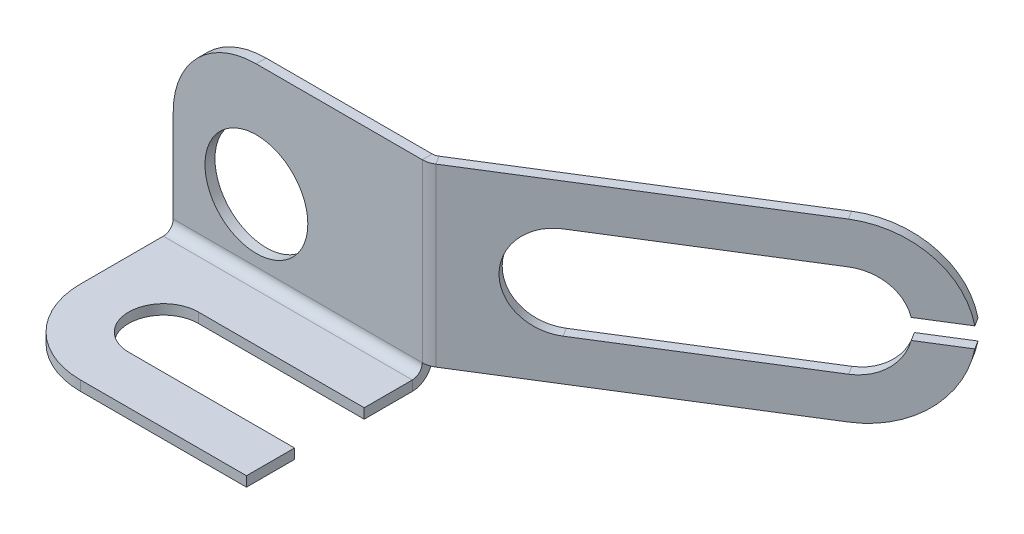
SolidWorks part; units mm, degrees
note: The reader was unsure of these and kept them because the rebuilt part matched: flange length of "Edge-Flange1", "Edge-Flange2".
ref_plane "Front Plane" through (0, 0, 0) normal (0, 0, 1) x (1, 0, 0)
ref_plane "Top Plane" through (0, 0, 0) normal (0, 1, 0) x (1, 0, 0)
ref_plane "Right Plane" through (0, 0, 0) normal (1, 0, 0) x (0, 0, -1)
sketch "Sketch1" plane through (0, 0, 0) normal (0, 1, 0) x (1, 0, 0)
  line L0 (-12.2638, 0) -> (10.2953, 0) construction
  line L1 (-8.4742, 5) -> (6.5404, 5)
  line L2 (-8.4742, 5) -> (-8.4742, 0)
  line L3 (-3.4742, -5) -> (6.5404, -5)
  line L5 (0, 0) -> (7.6969, 0) construction
  line L12 (6.5404, 5) -> (6.5404, -5)
  arc A0 (-8.4742, 0) -> (-3.4742, -5) centre (-3.4742, 0) ccw
  point P0 (0, 0)
  point P12 (3.8484, 0)
  dimension "D3" = 5
  dimension "D2" = 5
base flange "Base-Flange1" sketch "Sketch1" thickness 0.6 reverse thickness direction no parameters "D1"=0.7366
sketch "Sketch6" plane through (0, 0, 0) normal (0, 1, 0) x (1, 0, 0)
  line L0 (-8.4742, 0) -> (10.7229, 0) construction
  line L1 (6.5404, -2.1) -> (-3.4596, -2.1)
  line L2 (6.5404, -5) -> (6.5404, 5) construction
  line L3 (6.5404, 2.1) -> (-3.4596, 2.1)
  line L4 (6.5404, 2.1) -> (6.5404, -2.1)
  arc A0 (-3.4596, 2.1) -> (-3.4596, -2.1) centre (-3.4596, 0) ccw
  point P11 (0, 0)
  dimension "D2" = 2.1
  dimension "D1" = 10
extrude "Cut-Extrude1" cut sketch "Sketch6" against normal blind 10
edge flange "Edge-Flange1" sketch "Sketch9" flange angle 90 flange length 11.8 flange position bend outside bend radius 0.6 thickness 0.6 parameters "D6"=10
sketch "Sketch9" plane through (0, 0, -5) normal (0, 0, 1) x (1, 0, 0)
  line L2 (-8.4742, 0) -> (-8.4742, 11.2)
  line L3 (-8.4742, 11.2) -> (6.5404, 11.2)
  line L4 (6.5404, 11.2) -> (6.5404, 0)
  line L5 (6.5404, 0) -> (-8.4742, 0) construction
  line L6 (6.5404, 0) -> (-8.4742, 0)
bend "EdgeBend1" bend radius 0.6 bend angle 90 parameters "D5"=1
sketch "Sketch10" plane through (0, 0, -5.6) normal (0, 0, 1) x (1, 0, 0)
  line L0 (-8.4742, 11.2) -> (-8.4742, 0.6) construction
  line L1 (6.5404, 11.2) -> (-8.4742, 11.2) construction
  line L2 (-8.4742, 6.2) -> (-8.4742, 11.2)
  line L3 (-8.4742, 11.2) -> (-3.4742, 11.2)
  arc A0 (-8.4742, 6.2) -> (-3.4742, 11.2) centre (-3.4742, 6.2) cw
  dimension "D1" = 5
extrude "Cut-Extrude2" cut sketch "Sketch10" against normal blind 10
sketch "Sketch11" plane through (0, 0, -5.6) normal (0, 0, 1) x (1, 0, 0)
  line L0 (6.5404, -0.6) -> (-3.4596, -0.6) construction
  line L1 (6.5404, 0.6) -> (6.5404, 11.2) construction
  circle A0 centre (-3.4596, 4.4) radius 3.1
  point P4 (-3.1567, 4.4)
  point P5 (-3.7952, 4.4)
  dimension "D3" = 6.2
  dimension "D1" = 5
  dimension "D2" = 10
extrude "Cut-Extrude3" cut sketch "Sketch11" against normal blind 10
edge flange "Edge-Flange2" sketch "Sketch16" flange angle 148 flange length 24 flange position bend outside bend radius 0.6 thickness 0.6 parameters "D6"=10
sketch "Sketch16" plane through (6.5404, 0, -6.2) normal (-0.5299, 0, -0.848) x (0, 1, 0)
  line L2 (0.6, 0) -> (0.6, 23.828)
  line L3 (0.6, 23.828) -> (11.2, 23.828)
  line L4 (11.2, 23.828) -> (11.2, 0)
  line L5 (11.2, 0) -> (0.6, 0) construction
  line L6 (11.2, 0) -> (0.6, 0)
bend "EdgeBend2" bend radius 0.6 bend angle 32 parameters "D5"=2
sketch "Sketch17" plane through (-0.5834, 0, -0.9336) normal (0.5299, 0, 0.848) x (0.848, 0, -0.5299)
  line L0 (14.7141, 5.9) -> (27.2141, 5.9) construction
  line L1 (14.7141, 8.7) -> (27.2141, 8.7)
  line L2 (14.7141, 3.1) -> (27.2141, 3.1)
  line L3 (8.5141, 0.6) -> (8.5141, 11.2) construction
  line L4 (9.15, 11.2) -> (32.8059, 11.2) construction
  line L5 (32.8059, 11.2) -> (32.8059, 0.6) construction
  line L6 (32.8059, 0.6) -> (9.15, 0.6) construction
  line L7 (32.8059, 11.2) -> (32.8059, 0.6) construction
  line L8 (32.8059, 11.2) -> (32.8059, 0.6)
  line L9 (27.2059, 11.2) -> (32.8059, 11.2)
  line L10 (32.8059, 0.6) -> (27.2059, 0.6)
  arc A0 (14.7141, 8.7) -> (14.7141, 3.1) centre (14.7141, 5.9) ccw
  arc A1 (27.2141, 3.1) -> (27.2141, 8.7) centre (27.2141, 5.9) ccw
  arc A2 (27.2059, 11.2) -> (32.7979, 5.9) centre (27.2059, 5.6) cw
  arc A3 (27.2059, 0.6) -> (32.7979, 5.9) centre (27.2059, 6.2) ccw
  point P2 (20.9641, 5.9)
  dimension "D3" = 2.8
  dimension "D4" = 5.6
  dimension "D5" = 5.6
  dimension "D1" = 12.5
  dimension "D2" = 6.2
extrude "Cut-Extrude4" cut sketch "Sketch17" against normal blind 10
sketch "Sketch19" plane through (-0.5834, 0, -0.9336) normal (0.5299, 0, 0.848) x (0.848, 0, -0.5299)
  line L0 (32.7979, 5.9) -> (30.0141, 5.9) construction
  line L1 (32.7332, 5.3) -> (29.9491, 5.3)
  line L2 (32.7332, 6.5) -> (29.9491, 6.5)
  arc A0 (27.2141, 3.1) -> (27.2141, 8.7) centre (27.2141, 5.9) ccw construction
  arc A1 (27.2059, 0.6) -> (32.7979, 5.9) centre (27.2059, 6.2) ccw construction
  arc A2 (29.9491, 6.5) -> (29.9491, 5.3) centre (27.2141, 5.9) cw
  arc A3 (32.7332, 6.5) -> (32.7332, 5.3) centre (30.4025, 5.9) cw
  dimension "D1" = 0.6
extrude "Cut-Extrude5" cut sketch "Sketch19" against normal blind 10
sketch "Bend-Lines1" [suppressed] plane through (0, 0, 0) normal (0, 1, 0) x (1, 0, 0)
sketch "Bounding-Box1" [suppressed] plane through (0, 0, 0) normal (0, 1, 0) x (1, 0, 0)
sheet metal parameters "Sheet-Metal1" thickness 0.6 parameters "D1"=0.7366
flat pattern "Flat-Pattern1" [suppressed]
sketch "Bend-Lines2" plane through (0, 0, 0) normal (0, 1, 0) x (1, 0, 0)
sketch3d "Bounding-Box2" [suppressed]
  line L0 (5, -5, 0) -> (-10.0146, -5, 0) construction
  line L1 (5, 5, 0) -> (-10.0146, 5, 0) construction
  line L2 (5, -5, 0) -> (5, 5, 0) construction
  line L3 (-10.0146, -5, 0) -> (-10.0146, 5, 0) construction
sheet metal parameters "Sheet-Metal2" thickness 0.6 parameters "D1"=0.7366
flat pattern "Flat-Pattern1"
sketch "Bend-Lines2" plane through (0, 0, 0) normal (0, 1, 0) x (1, 0, 0)
sketch3d "Bounding-Box2" [suppressed]
  line L0 (-5, -5, 0) -> (10.0146, -5, 0) construction
  line L1 (-5, 5, 0) -> (10.0146, 5, 0) construction
  line L2 (-5, -5, 0) -> (-5, 5, 0) construction
  line L3 (10.0146, -5, 0) -> (10.0146, 5, 0) construction
sheet metal parameters "Sheet-Metal3" thickness 0.6 parameters "D1"=0.7366
flat pattern "Flat-Pattern1"
sketch "Bend-Lines2" plane through (0, 0, 0) normal (0, 1, 0) x (1, 0, 0)
  line L0 (6.5404, 5.7069) -> (-8.4742, 5.7069) construction
  line L1 (6.5404, 5.7069) -> (-8.4742, 5.7069) construction
sketch3d "Bounding-Box2" [suppressed]
  line L0 (10.0146, 17.0137, 0) -> (10.0146, -5, 0) construction
  line L1 (-5, 17.0137, 0) -> (-5, -5, 0) construction
  line L2 (10.0146, 17.0137, 0) -> (-5, 17.0137, 0) construction
  line L3 (10.0146, -5, 0) -> (-5, -5, 0) construction
bend of the flat pattern "Flatten-<EdgeBend1>1"
sheet metal parameters "Sheet-Metal4" thickness 0.6 parameters "D1"=0.7366
flat pattern "Flat-Pattern1"
sketch "Bend-Lines2" plane through (0, 0, 0) normal (0, 1, 0) x (1, 0, 0)
  line L0 (6.5404, 5.7069) -> (-8.4742, 5.7069) construction
  line L1 (6.5404, 5.7069) -> (-8.4742, 5.7069) construction
sketch3d "Bounding-Box2" [suppressed]
  line L0 (10.0146, 17.0137, 0) -> (10.0146, -5, 0) construction
  line L1 (-5, 17.0137, 0) -> (-5, -5, 0) construction
  line L2 (10.0146, 17.0137, 0) -> (-5, 17.0137, 0) construction
  line L3 (10.0146, -5, 0) -> (-5, -5, 0) construction
bend of the flat pattern "Flatten-<EdgeBend1>1"
sheet metal parameters "Sheet-Metal5" thickness 0.6 parameters "D1"=0.7366
flat pattern "Flat-Pattern1"
sketch "Bend-Lines2" plane through (0, 0, 0) normal (0, 1, 0) x (1, 0, 0)
  line L0 (6.5404, 5.7069) -> (-8.4742, 5.7069) construction
  line L1 (6.5404, 5.7069) -> (-8.4742, 5.7069) construction
sketch3d "Bounding-Box2" [suppressed]
  line L0 (10.0146, 17.0137, 0) -> (10.0146, -5, 0) construction
  line L1 (-5, 17.0137, 0) -> (-5, -5, 0) construction
  line L2 (10.0146, 17.0137, 0) -> (-5, 17.0137, 0) construction
  line L3 (10.0146, -5, 0) -> (-5, -5, 0) construction
bend of the flat pattern "Flatten-<EdgeBend1>1"
sheet metal parameters "Sheet-Metal6" thickness 0.6 parameters "D1"=0.7366
flat pattern "Flat-Pattern1" [suppressed]
sketch "Bend-Lines2" plane through (0, 0, 0) normal (0, 1, 0) x (1, 0, 0)
  line L0 (6.5404, 5.7069) -> (-8.4742, 5.7069) construction
  line L1 (6.5404, 5.7069) -> (-8.4742, 5.7069) construction
  line L2 (6.7918, 6.4137) -> (6.7918, 17.0137) construction
  line L3 (6.7918, 6.4137) -> (6.7918, 17.0137) construction
sketch3d "Bounding-Box2" [suppressed]
  line L0 (-5, -5, 0) -> (34.1732, -5, 0) construction
  line L1 (-5, 17.0137, 0) -> (34.1732, 17.0137, 0) construction
  line L2 (-5, -5, 0) -> (-5, 17.0137, 0) construction
  line L3 (34.1732, -5, 0) -> (34.1732, 17.0137, 0) construction
bend of the flat pattern "Flatten-<EdgeBend1>1"
bend of the flat pattern "Flatten-<EdgeBend2>1"
sketch "Sketch17-1" [suppressed] plane through (-2.107, 0, -5.8137) normal (0, 1, 0) x (1, 0, 0)
  line L0 (14.7141, 5.9) -> (27.2141, 5.9) construction
  line L1 (14.7141, 7.6978) -> (27.2141, 7.6978)
  line L2 (14.7141, 4.1022) -> (27.2141, 4.1022)
  line L3 (8.5141, 0.6) -> (8.5141, 11.2) construction
  arc A0 (14.7141, 7.6978) -> (14.7141, 4.1022) centre (14.7141, 5.9) ccw
  arc A1 (27.2141, 4.1022) -> (27.2141, 7.6978) centre (27.2141, 5.9) ccw
  point P2 (20.9641, 5.9)
  dimension "D1" = 12.5
  dimension "D2" = 6.2
sheet metal parameters "Sheet-Metal7" thickness 0.6 parameters "D1"=0.7366
flat pattern "Flat-Pattern1" [suppressed]
sketch "Bend-Lines2" plane through (0, 0, 0) normal (0, 1, 0) x (1, 0, 0)
  line L0 (6.5404, 5.7069) -> (-8.4742, 5.7069) construction
  line L1 (6.5404, 5.7069) -> (-8.4742, 5.7069) construction
  line L2 (6.7918, 6.4137) -> (6.7918, 17.0137) construction
  line L3 (6.7918, 6.4137) -> (6.7918, 17.0137) construction
sketch3d "Bounding-Box2" [suppressed]
  line L0 (34.1651, -5, 0) -> (-5, -5, 0) construction
  line L1 (34.1651, 17.0137, 0) -> (-5, 17.0137, 0) construction
  line L2 (34.1651, -5, 0) -> (34.1651, 17.0137, 0) construction
  line L3 (-5, -5, 0) -> (-5, 17.0137, 0) construction
bend of the flat pattern "Flatten-<EdgeBend1>1"
bend of the flat pattern "Flatten-<EdgeBend2>1"
sketch "Sketch17-1" [suppressed] plane through (-2.107, 0, -5.8137) normal (0, 1, 0) x (1, 0, 0)
  line L0 (14.7141, 5.9) -> (27.2141, 5.9) construction
  line L1 (14.7141, 8.7) -> (27.2141, 8.7)
  line L2 (14.7141, 3.1) -> (27.2141, 3.1)
  line L3 (8.5141, 0.6) -> (8.5141, 11.2) construction
  line L8 (32.8059, 11.2) -> (32.8059, 0.6)
  line L9 (27.2059, 11.2) -> (32.8059, 11.2)
  line L10 (32.8059, 0.6) -> (27.2059, 0.6)
  arc A0 (14.7141, 8.7) -> (14.7141, 3.1) centre (14.7141, 5.9) ccw
  arc A1 (27.2141, 3.1) -> (27.2141, 8.7) centre (27.2141, 5.9) ccw
  arc A2 (27.2059, 11.2) -> (32.7979, 5.9) centre (27.2059, 5.6) cw
  arc A3 (27.2059, 0.6) -> (32.7979, 5.9) centre (27.2059, 6.2) ccw
  point P2 (20.9641, 5.9)
  dimension "D3" = 2.8
  dimension "D4" = 5.6
  dimension "D5" = 5.6
  dimension "D1" = 12.5
  dimension "D2" = 6.2
sheet metal parameters "Sheet-Metal8" thickness 0.6 parameters "D1"=0.7366
flat pattern "Flat-Pattern1" [suppressed]
sketch "Bend-Lines2" plane through (0, 0, 0) normal (0, 1, 0) x (1, 0, 0)
  line L0 (6.5404, 5.7069) -> (-8.4742, 5.7069) construction
  line L1 (6.5404, 5.7069) -> (-8.4742, 5.7069) construction
  line L2 (6.7918, 6.4137) -> (6.7918, 17.0137) construction
  line L3 (6.7918, 6.4137) -> (6.7918, 17.0137) construction
sketch3d "Bounding-Box2" [suppressed]
  line L0 (-5, -5, 0) -> (34.1004, -5, 0) construction
  line L1 (-5, 17.0137, 0) -> (34.1004, 17.0137, 0) construction
  line L2 (-5, -5, 0) -> (-5, 17.0137, 0) construction
  line L3 (34.1004, -5, 0) -> (34.1004, 17.0137, 0) construction
bend of the flat pattern "Flatten-<EdgeBend1>1"
bend of the flat pattern "Flatten-<EdgeBend2>1"
sketch "Sketch17-1" [suppressed] plane through (-2.107, 0, -5.8137) normal (0, 1, 0) x (1, 0, 0)
  line L0 (14.7141, 5.9) -> (27.2141, 5.9) construction
  line L1 (14.7141, 8.7) -> (27.2141, 8.7)
  line L2 (14.7141, 3.1) -> (27.2141, 3.1)
  line L3 (8.5141, 0.6) -> (8.5141, 11.2) construction
  line L8 (32.8059, 11.2) -> (32.8059, 0.6)
  line L9 (27.2059, 11.2) -> (32.8059, 11.2)
  line L10 (32.8059, 0.6) -> (27.2059, 0.6)
  arc A0 (14.7141, 8.7) -> (14.7141, 3.1) centre (14.7141, 5.9) ccw
  arc A1 (27.2141, 3.1) -> (27.2141, 8.7) centre (27.2141, 5.9) ccw
  arc A2 (27.2059, 11.2) -> (32.7979, 5.9) centre (27.2059, 5.6) cw
  arc A3 (27.2059, 0.6) -> (32.7979, 5.9) centre (27.2059, 6.2) ccw
  point P2 (20.9641, 5.9)
  dimension "D3" = 2.8
  dimension "D4" = 5.6
  dimension "D5" = 5.6
  dimension "D1" = 12.5
  dimension "D2" = 6.2
